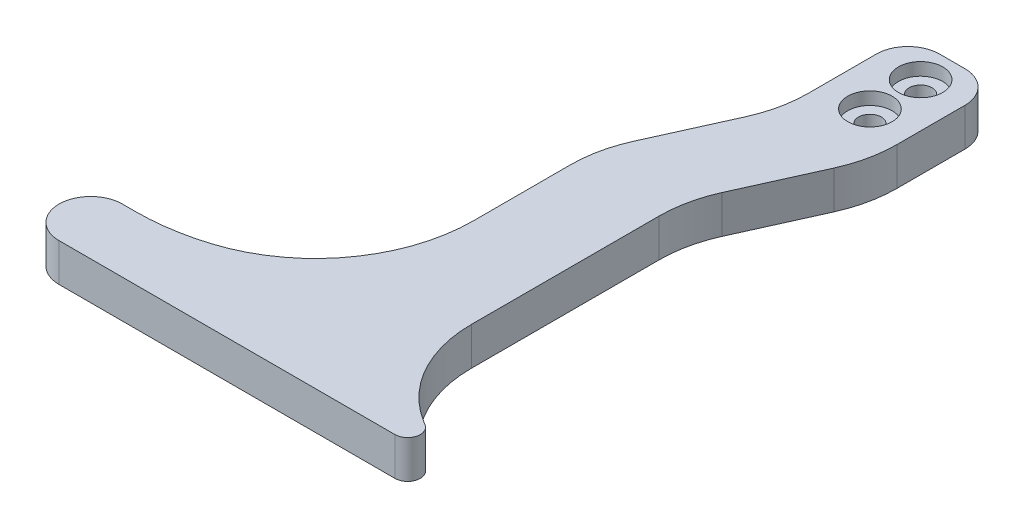
SolidWorks part; units mm, degrees
ref_plane "Front Plane" through (0, 0, 0) normal (0, 0, 1) x (1, 0, 0)
ref_plane "Top Plane" through (0, 0, 0) normal (0, 1, 0) x (1, 0, 0)
ref_plane "Right Plane" through (0, 0, 0) normal (1, 0, 0) x (0, 0, -1)
sketch "Sketch1" plane through (0, 0, 0) normal (0, 1, 0) x (1, 0, 0)
  line L1 (0, 0) -> (17.78, 0)
  line L2 (17.78, 0) -> (17.78, -25.4)
  line L5 (26.67, -120.65) -> (-55.88, -120.65)
  line L6 (17.78, -25.4) -> (6.35, -50.8)
  line L7 (6.35, -50.8) -> (6.35, -107.95)
  line L8 (6.35, -107.95) -> (26.67, -120.65)
  line L9 (0, -25.4) -> (-11.43, -50.8)
  line L10 (-11.43, -50.8) -> (-11.43, -90.17)
  line L11 (-11.43, -90.17) -> (-5.08, -107.95)
  line L12 (0, -25.4) -> (0, 0)
  line L14 (-55.88, -120.65) -> (-55.88, -107.95)
  line L15 (-55.88, -107.95) -> (-5.08, -107.95)
  circle A0 centre (8.89, -6.35) radius 2.286
  circle A1 centre (8.89, -16.51) radius 2.286
  point P0 (6.35, -107.95)
  point P12 (8.89, 0)
  point P21 (-42.3698, -120.65)
  dimension "D5" = 4.572
  dimension "D2" = 12.7
  dimension "D3" = 17.78
  dimension "D4" = 17.78
  dimension "D6" = 6.35
  dimension "D7" = 10.16
  dimension "D8" = 25.4
  dimension "D9" = 11.43
  dimension "D10" = 25.4
  dimension "D11" = 39.37
  dimension "D12" = 17.78
  dimension "D13" = 31.75
  dimension "D14" = 6.35
  dimension "D15" = 50.8
extrude "Boss-Extrude1" add sketch "Sketch1" along normal blind 7.62
sketch "Sketch2" plane through (0, 0, 0) normal (0, -1, 0) x (1, 0, 0)
  circle A0 centre (8.89, 6.35) radius 4.318
  circle A1 centre (8.89, 16.51) radius 4.318
  circle M1 centre (8.89, 6.35) radius 2.286
  circle M8 centre (8.89, 16.51) radius 2.286
  dimension "D1" = 8.636
extrude "Boss-Extrude3" [suppressed] add sketch "Sketch2" along normal blind 2.54 contours A0 A1 M8 | A1 A0 M1 | A0 A1
fillet "Fillet1" radius 25.4 5 edges at (6.35, 3.81, 107.95) (-11.43, 3.81, 50.8) (17.78, 3.81, 25.4) (6.35, 3.81, 50.8) (0, 3.81, 25.4)
fillet "Fillet3" radius 44.45 1 edges at (-5.08, 3.81, 107.95)
fillet "Fillet2" radius 6.35 4 edges at (17.78, 3.81, 0) (0, 3.81, 0) (-55.88, 3.81, 120.65) (-55.88, 3.81, 107.95)
fillet "Fillet4" radius 31.75 1 edges at (-11.43, 3.81, 90.17)
sketch "Sketch3" plane through (0, 7.62, 0) normal (0, 1, 0) x (1, 0, 0)
  circle A0 centre (8.89, -6.35) radius 4.445
  circle A1 centre (8.89, -16.51) radius 4.445
  dimension "D1" = 8.89
extrude "Cut-Extrude1" cut sketch "Sketch3" against normal blind 2.54
fillet "Fillet5" radius 2.54 1 edges at (26.67, 3.81, 120.65)
